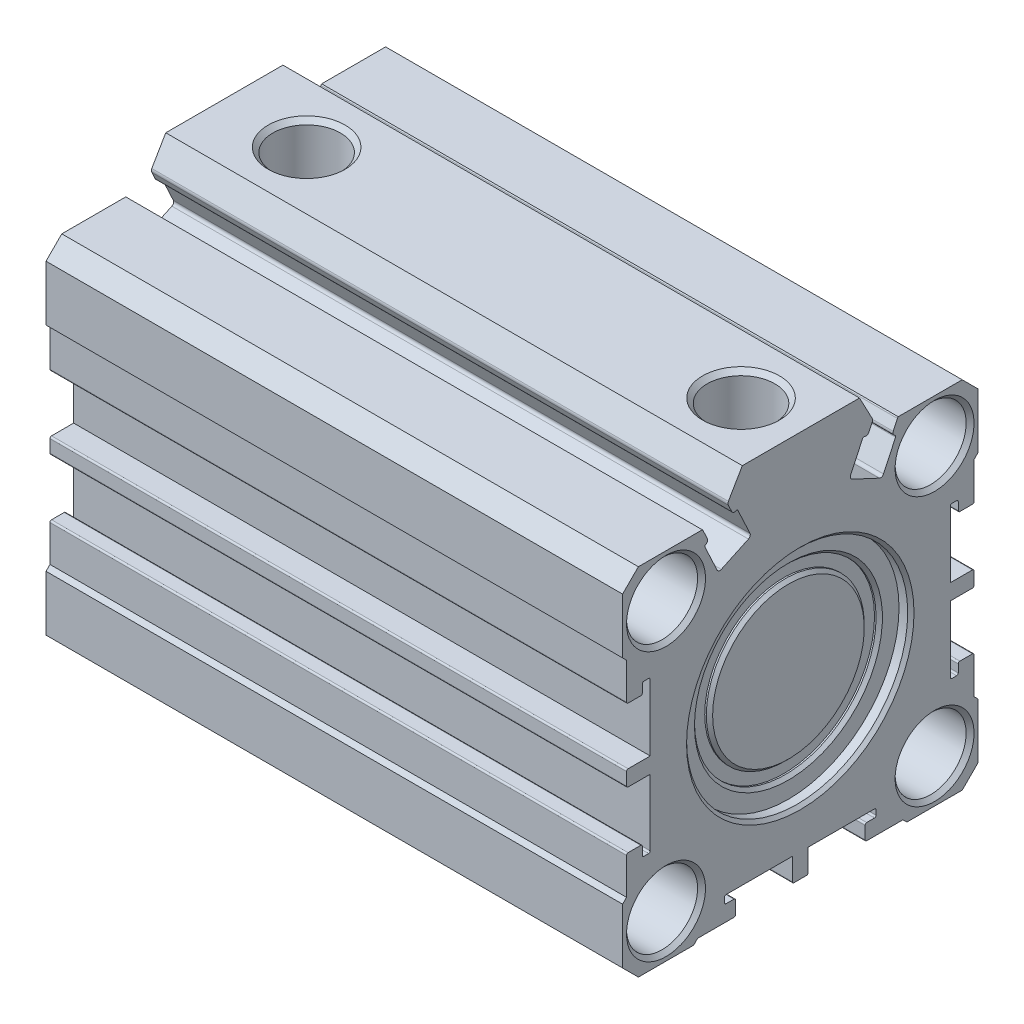
SolidWorks part; units mm, degrees
ref_plane "前视基准面" through (0, 0, 0) normal (0, 0, 1) x (1, 0, 0)
ref_plane "上视基准面" through (0, 0, 0) normal (0, 1, 0) x (1, 0, 0)
ref_plane "右视基准面" through (0, 0, 0) normal (1, 0, 0) x (0, 0, -1)
sketch "草图1" plane through (0, 0, 0) normal (1, 0, 0) x (0, 0, -1)
  line L0 (-22.5, -20.5) -> (-20.5, -22.5)
  line L1 (-20.5, -22.5) -> (-13.5, -22.5)
  line L2 (-13.5, -22.5) -> (-13, -22)
  line L3 (-13, -22) -> (-8.4, -22)
  line L4 (-8.2, -21.8) -> (-8.2, -20.2)
  line L5 (-8.4, -20) -> (-9.4, -20)
  line L6 (-9.6, -19.8) -> (-9.6, -19.2)
  line L7 (-9.4, -19) -> (-1, -19)
  line L8 (-1, -19) -> (-1, -21.8)
  line L9 (-0.8, -22) -> (0.8, -22)
  line L10 (1, -21.8) -> (1, -19)
  line L11 (1, -19) -> (9.4, -19)
  line L12 (9.6, -19.2) -> (9.6, -19.8)
  line L13 (9.4, -20) -> (8.4, -20)
  line L14 (8.2, -20.2) -> (8.2, -21.8)
  line L15 (8.4, -22) -> (13, -22)
  line L16 (13, -22) -> (13.5, -22.5)
  line L17 (13.5, -22.5) -> (20.5, -22.5)
  line L18 (20.5, -22.5) -> (22.5, -20.5)
  line L19 (22.5, -20.5) -> (22.5, -13.5)
  line L20 (22.5, -13.5) -> (22, -13)
  line L21 (22, -13) -> (22, -8.4)
  line L22 (21.8, -8.2) -> (20.2, -8.2)
  line L23 (20, -8.4) -> (20, -9.4)
  line L24 (19.8, -9.6) -> (19.2, -9.6)
  line L25 (19, -9.4) -> (19, -1)
  line L26 (19, -1) -> (21.8, -1)
  line L27 (22, -0.8) -> (22, 0.8)
  line L28 (21.8, 1) -> (19, 1)
  line L29 (19, 1) -> (19, 9.4)
  line L30 (19.2, 9.6) -> (19.8, 9.6)
  line L31 (20, 9.4) -> (20, 8.4)
  line L32 (20.2, 8.2) -> (21.8, 8.2)
  line L33 (22, 8.4) -> (22, 13)
  line L34 (22, 13) -> (22.5, 13.5)
  line L35 (22.5, 13.5) -> (22.5, 20.5)
  line L36 (22.5, 20.5) -> (20.5, 22.5)
  line L37 (20.5, 22.5) -> (12.3991, 22.5)
  line L38 (12.303, 22.3613) -> (11.7681, 21.2142)
  line L39 (12.0583, 20.4168) -> (10.5369, 17.1541)
  line L40 (10.0053, 16.9607) -> (6.5613, 18.5666)
  line L41 (6.3679, 19.0982) -> (7.8893, 22.3609)
  line L42 (8.6866, 22.6511) -> (9.1023, 23.5426)
  line L43 (9.0912, 23.9875) -> (7.499, 27)
  line L44 (7.499, 27) -> (-7.3373, 27)
  line L45 (-7.3373, 27) -> (-9.1053, 23.9744)
  line L46 (-9.1023, 23.5426) -> (-8.6866, 22.6511)
  line L47 (-7.8893, 22.3609) -> (-6.3679, 19.0982)
  line L48 (-6.5613, 18.5666) -> (-10.0053, 16.9607)
  line L49 (-10.5369, 17.1541) -> (-12.0583, 20.4168)
  line L50 (-11.7681, 21.2142) -> (-12.303, 22.3613)
  line L51 (-12.3991, 22.5) -> (-20.5, 22.5)
  line L52 (-20.5, 22.5) -> (-22.5, 20.5)
  line L53 (-22.5, 20.5) -> (-22.5, 13.5)
  line L54 (-22.5, 13.5) -> (-22, 13)
  line L55 (-22, 13) -> (-22, 8.4)
  line L56 (-21.8, 8.2) -> (-20.2, 8.2)
  line L57 (-20, 8.4) -> (-20, 9.4)
  line L58 (-19.8, 9.6) -> (-19.2, 9.6)
  line L59 (-19, 9.4) -> (-19, 1)
  line L60 (-19, 1) -> (-21.8, 1)
  line L61 (-22, 0.8) -> (-22, -0.8)
  line L62 (-21.8, -1) -> (-19, -1)
  line L63 (-19, -1) -> (-19, -9.4)
  line L64 (-19.2, -9.6) -> (-19.8, -9.6)
  line L65 (-20, -9.4) -> (-20, -8.4)
  line L66 (-20.2, -8.2) -> (-21.8, -8.2)
  line L67 (-22, -8.4) -> (-22, -13)
  line L68 (-22, -13) -> (-22.5, -13.5)
  line L69 (-22.5, -13.5) -> (-22.5, -20.5)
  arc A0 (-8.4, -22) -> (-8.2, -21.8) centre (-8.4, -21.8) ccw
  arc A1 (-8.2, -20.2) -> (-8.4, -20) centre (-8.4, -20.2) ccw
  arc A2 (-9.4, -20) -> (-9.6, -19.8) centre (-9.4, -19.8) cw
  arc A3 (-9.6, -19.2) -> (-9.4, -19) centre (-9.4, -19.2) cw
  arc A4 (-1, -21.8) -> (-0.8, -22) centre (-0.8, -21.8) ccw
  arc A5 (0.8, -22) -> (1, -21.8) centre (0.8, -21.8) ccw
  arc A6 (9.4, -19) -> (9.6, -19.2) centre (9.4, -19.2) cw
  arc A7 (9.6, -19.8) -> (9.4, -20) centre (9.4, -19.8) cw
  arc A8 (8.4, -20) -> (8.2, -20.2) centre (8.4, -20.2) ccw
  arc A9 (8.2, -21.8) -> (8.4, -22) centre (8.4, -21.8) ccw
  arc A10 (22, -8.4) -> (21.8, -8.2) centre (21.8, -8.4) ccw
  arc A11 (20.2, -8.2) -> (20, -8.4) centre (20.2, -8.4) ccw
  arc A12 (20, -9.4) -> (19.8, -9.6) centre (19.8, -9.4) cw
  arc A13 (19.2, -9.6) -> (19, -9.4) centre (19.2, -9.4) cw
  arc A14 (21.8, -1) -> (22, -0.8) centre (21.8, -0.8) ccw
  arc A15 (22, 0.8) -> (21.8, 1) centre (21.8, 0.8) ccw
  arc A16 (19, 9.4) -> (19.2, 9.6) centre (19.2, 9.4) cw
  arc A17 (19.8, 9.6) -> (20, 9.4) centre (19.8, 9.4) cw
  arc A18 (20, 8.4) -> (20.2, 8.2) centre (20.2, 8.4) ccw
  arc A19 (21.8, 8.2) -> (22, 8.4) centre (21.8, 8.4) ccw
  arc A20 (12.3991, 22.5) -> (12.303, 22.3613) centre (12.7561, 22.15) ccw
  arc A21 (11.7681, 21.2142) -> (11.9616, 20.6826) centre (12.1306, 21.0452) ccw
  arc A22 (11.9616, 20.6826) -> (12.0583, 20.4168) centre (11.877, 20.5014) cw
  arc A23 (10.5369, 17.1541) -> (10.0053, 16.9607) centre (10.1744, 17.3232) cw
  arc A24 (6.5613, 18.5666) -> (6.3679, 19.0982) centre (6.7304, 18.9291) cw
  arc A25 (7.8893, 22.3609) -> (8.1551, 22.4576) centre (8.0705, 22.2764) cw
  arc A26 (8.1551, 22.4576) -> (8.6866, 22.6511) centre (8.3241, 22.8201) ccw
  arc A27 (9.1023, 23.5426) -> (9.0912, 23.9875) centre (8.6492, 23.7539) ccw
  arc A28 (-9.1053, 23.9744) -> (-9.1023, 23.5426) centre (-8.6107, 23.7619) ccw
  arc A29 (-8.6866, 22.6511) -> (-8.1551, 22.4576) centre (-8.3241, 22.8201) ccw
  arc A30 (-8.1551, 22.4576) -> (-7.8893, 22.3609) centre (-8.0705, 22.2764) cw
  arc A31 (-6.3679, 19.0982) -> (-6.5613, 18.5666) centre (-6.7304, 18.9291) cw
  arc A32 (-10.0053, 16.9607) -> (-10.5369, 17.1541) centre (-10.1744, 17.3232) cw
  arc A33 (-12.0583, 20.4168) -> (-11.9616, 20.6826) centre (-11.877, 20.5014) cw
  arc A34 (-11.9616, 20.6826) -> (-11.7681, 21.2142) centre (-12.1306, 21.0452) ccw
  arc A35 (-12.303, 22.3613) -> (-12.3991, 22.5) centre (-12.7561, 22.15) ccw
  arc A36 (-22, 8.4) -> (-21.8, 8.2) centre (-21.8, 8.4) ccw
  arc A37 (-20.2, 8.2) -> (-20, 8.4) centre (-20.2, 8.4) ccw
  arc A38 (-20, 9.4) -> (-19.8, 9.6) centre (-19.8, 9.4) cw
  arc A39 (-19.2, 9.6) -> (-19, 9.4) centre (-19.2, 9.4) cw
  arc A40 (-21.8, 1) -> (-22, 0.8) centre (-21.8, 0.8) ccw
  arc A41 (-22, -0.8) -> (-21.8, -1) centre (-21.8, -0.8) ccw
  arc A42 (-19, -9.4) -> (-19.2, -9.6) centre (-19.2, -9.4) cw
  arc A43 (-19.8, -9.6) -> (-20, -9.4) centre (-19.8, -9.4) cw
  arc A44 (-20, -8.4) -> (-20.2, -8.2) centre (-20.2, -8.4) ccw
  arc A45 (-21.8, -8.2) -> (-22, -8.4) centre (-21.8, -8.4) ccw
extrude "凸台-拉伸1" add sketch "草图1" along normal blind 73
ref_plane "基准面1" through (0, 0, 17) normal (0, 0, 1) x (1, 0, 0)
sketch "草图2" plane through (0, 0, 17) normal (0, 0, 1) x (1, 0, 0)
  line L0 (0, -17) -> (0, -12)
  line L1 (0, -12) -> (0.5, -12.5)
  line L2 (0.5, -12.5) -> (7, -12.5)
  line L3 (7, -12.5) -> (7, -14)
  line L4 (7, -14) -> (7.5415, -14.5415)
  line L5 (7.5415, -14.5415) -> (36.5, -14.5415)
  line L6 (36.5, -14.5415) -> (36.5, -17)
  line L7 (36.5, -17) -> (0, -17)
  line L8 (36.5, -17) -> (0, -17) construction
revolve "切除-旋转1" cut sketch "草图2" angle 360 about L8 reverse direction yes
cosmetic thread "装饰螺纹线1" parameters "D1"=10, "D2"=6
cosmetic thread "装饰螺纹线2" parameters "D1"=10, "D2"=6
sketch "草图3" plane through (0, 0, 0) normal (1, 0, 0) x (0, 0, -1)
  line L0 (-17, -17) -> (17, -17)
  line L1 (-17, -17) -> (-17, 17)
pattern_linear "阵列(线性)1" count 2 spacing 34 along (0, 0, -1) count 2 spacing 34 along (0, 1, 0) of "切除-旋转1"
sketch "草图4" plane through (0, 0, 17) normal (0, 0, 1) x (1, 0, 0)
  line L0 (36.5, -17) -> (36.5, -14.5415)
  line L1 (36.5, -14.5415) -> (65.4585, -14.5415)
  line L2 (65.4585, -14.5415) -> (66, -14)
  line L3 (66, -14) -> (66, -12.5)
  line L4 (66, -12.5) -> (72.5, -12.5)
  line L5 (72.5, -12.5) -> (73, -12)
  line L6 (73, -12) -> (73, -17)
  line L7 (73, -17) -> (36.5, -17)
  line L8 (73, -17) -> (36.5, -17) construction
revolve "切除-旋转2" cut sketch "草图4" angle 360 about L8 reverse direction yes
ref_plane "基准面2" through (73, 0, 0) normal (1, 0, 0) x (0, 0, -1)
sketch "草图5" plane through (73, 0, 0) normal (1, 0, 0) x (0, 0, -1)
  line L0 (-17, -17) -> (17, -17)
  line L1 (-17, -17) -> (-17, 17)
pattern_linear "阵列(线性)2" count 2 spacing 34 along (0, 0, -1) count 2 spacing 34 along (0, 1, 0) of "切除-旋转2"
sketch "草图6" plane through (0, 0, 0) normal (0, 0, 1) x (1, 0, 0)
  line L0 (0, 0) -> (0, 8)
  line L1 (0, 8) -> (10.5, 8)
  line L2 (10.5, 8) -> (10.5, 16)
  line L3 (10.5, 16) -> (68.5, 16)
  line L4 (68.5, 16) -> (68.5, 0)
  line L5 (68.5, 0) -> (0, 0)
  line L6 (68.5, 0) -> (0, 0) construction
revolve "切除-旋转3" cut sketch "草图6" angle 360 about L6 reverse direction yes
sketch "草图7" plane through (0, 0, 0) normal (0, 0, 1) x (1, 0, 0)
  line L0 (0, 0) -> (0, 17.4)
  line L1 (0, 17.4) -> (0.4, 17)
  line L2 (0.4, 17) -> (3.1, 17)
  line L3 (3.1, 17) -> (3.1, 0)
  line L4 (3.1, 0) -> (0, 0)
  line L5 (3.1, 0) -> (0, 0) construction
revolve "切除-旋转4" cut sketch "草图7" angle 360 about L5 reverse direction yes
ref_plane "基准面3" through (1.6, 0, 0) normal (1, 0, 0) x (0, 0, -1)
hole_wizard "孔1" positions "草图9" profile "草图8" legacy
sketch "草图9" plane through (0, 27, 0) normal (0, 1, 0) x (1, 0, 0)
  point P0 (10.5, 0)
sketch "草图8" plane through (10.5, 27, 0) normal (1, 0, 0) x (0, 0, 1)
  line L0 (0, 0) -> (0, 8)
  line L1 (0, 8) -> (4.283, 8)
  line L2 (4.283, 8) -> (4.283, 0.581)
  line L3 (4.283, 0.581) -> (4.864, 0)
  line L4 (4.864, 0) -> (0, 0)
  line L5 (0, -6.4453) -> (0, 115.525) construction
  line L6 (-4.283, 0.581) -> (-4.864, 0) construction
  dimension "直径" = 8.566
  dimension "深度" = 8
  dimension "锥坑角度" = 90
  dimension "锥坑直径" = 9.728
cosmetic thread "装饰螺纹线3" parameters "D1"=8, "D2"=9.728
hole_wizard "孔2" positions "草图11" profile "草图10" legacy
sketch "草图11" plane through (0, 27, 0) normal (0, 1, 0) x (1, 0, 0)
  point P0 (65.5, 0)
sketch "草图10" plane through (65.5, 27, 0) normal (1, 0, 0) x (0, 0, 1)
  line L0 (0, 0) -> (0, 8)
  line L1 (0, 8) -> (4.283, 8)
  line L2 (4.283, 8) -> (4.283, 0.581)
  line L3 (4.283, 0.581) -> (4.864, 0)
  line L4 (4.864, 0) -> (0, 0)
  line L5 (0, -6.4453) -> (0, 115.525) construction
  line L6 (-4.283, 0.581) -> (-4.864, 0) construction
  dimension "直径" = 8.566
  dimension "深度" = 8
  dimension "锥坑角度" = 90
  dimension "锥坑直径" = 9.728
cosmetic thread "装饰螺纹线4" parameters "D1"=8, "D2"=9.728
sketch "草图12" plane through (0, 0, 0) normal (0, 0, 1) x (1, 0, 0)
  line L0 (0.6, 8) -> (3.1, 8)
  line L1 (3.1, 8) -> (3.1, 11.5)
  line L2 (3.1, 11.5) -> (1.1, 11.5)
  line L3 (0.6, 11) -> (0.6, 8)
  line L4 (3.1, 0) -> (0.6, 0) construction
  arc A0 (1.1, 11.5) -> (0.6, 11) centre (1.1, 11) ccw
revolve "旋转1" add sketch "草图12" angle 360 about L4 reverse direction yes
hole_wizard "孔3" positions "草图14" profile "草图13" legacy
sketch "草图14" plane through (73, 0, 0) normal (1, 0, 0) x (0, 0, -1)
  point P0 (0, 0)
sketch "草图13" plane through (73, 0, 0) normal (0, 1, 0) x (0, 0, -1)
  line L0 (0, 0) -> (0, 1.5)
  line L1 (0, 1.5) -> (14, 1.5)
  line L2 (14, 1.5) -> (14, 0.4)
  line L3 (14, 0.4) -> (14.4, 0)
  line L4 (14.4, 0) -> (0, 0)
  line L5 (0, -6.4453) -> (0, 115.525) construction
  line L6 (-14, 0.4) -> (-14.4, 0) construction
  dimension "直径" = 28
  dimension "深度" = 1.5
  dimension "锥坑角度" = 90
  dimension "锥坑直径" = 28.8
ref_plane "基准面4" through (73, 0, 0) normal (1, 0, 0) x (0, 0, -1)
ref_plane "基准面5" through (0, 19, 0) normal (0, 1, 0) x (1, 0, 0)
sketch "草图15" plane through (0, 0, 0) normal (0, 0, 1) x (1, 0, 0)
  line L0 (70.9, 11.5) -> (70.9, 10)
  line L1 (70.9, 10) -> (71.1, 10)
  line L2 (71.1, 10) -> (71.5, 9.6)
  line L3 (71.5, 9.6) -> (71.5, 11.9)
  line L4 (71.5, 11.9) -> (71.1, 11.5)
  line L5 (71.1, 11.5) -> (70.9, 11.5)
  line L6 (50, 0) -> (-50, 0) construction
revolve "切除-旋转5" cut sketch "草图15" angle 360 about L6 reverse direction yes
ref_plane "基准面6" through (1, 0, 0) normal (1, 0, 0) x (0, 0, -1)
ref_plane "基准面7" through (72, 0, 0) normal (1, 0, 0) x (0, 0, -1)
ref_plane "IP_SWITCH1 XY" through (1, 0, 0) normal (-1, 0, 0) x (0, 0, 1)
ref_plane "IP_SWITCH1 XZ" through (0, 17.7636, 0) normal (0, 1, 0) x (1, 0, 0)
ref_plane "IP_SWITCH1 YZ" through (0, 0, -8.2833) normal (0, 0, -1) x (-1, 0, 0)
ref_axis "IP_SWITCH1 X" through (1, 17.7636, 80.9) along (0, 0, -1)
ref_axis "IP_SWITCH1 Y" through (1, 50, -8.2833) along (0, -1, 0)
ref_axis "IP_SWITCH1 Z" through (-80.9, 17.7636, -8.2833) along (1, 0, 0)
sketch3d "IP_SWITCH1"
  point P0 (1, 17.7636, -8.2833)
ref_plane "IP_SWITCH2 XY" through (72, 0, 0) normal (1, 0, 0) x (0, 0, -1)
ref_plane "IP_SWITCH2 XZ" through (0, 17.7636, 0) normal (0, -1, 0) x (-1, 0, 0)
ref_plane "IP_SWITCH2 YZ" through (0, 0, 8.2833) normal (0, 0, -1) x (-1, 0, 0)
ref_axis "IP_SWITCH2 X" through (72, 17.7636, 80.9) along (0, 0, -1)
ref_axis "IP_SWITCH2 Y" through (72, -50, 8.2833) along (0, 1, 0)
ref_axis "IP_SWITCH2 Z" through (80.9, 17.7636, 8.2833) along (-1, 0, 0)
sketch3d "IP_SWITCH2"
  point P0 (72, 17.7636, 8.2833)
ref_plane "IP_SWITCH3 XY" through (1, 0, 0) normal (-1, 0, 0) x (0, 0, 1)
ref_plane "IP_SWITCH3 XZ" through (0, 1, 0) normal (0, 1, 0) x (1, 0, 0)
ref_plane "IP_SWITCH3 YZ" through (0, 0, -19) normal (0, 0, -1) x (-1, 0, 0)
ref_axis "IP_SWITCH3 X" through (1, 1, 80.9) along (0, 0, -1)
ref_axis "IP_SWITCH3 Y" through (1, 50, -19) along (0, -1, 0)
ref_axis "IP_SWITCH3 Z" through (-80.9, 1, -19) along (1, 0, 0)
sketch3d "IP_SWITCH3"
  point P0 (1, 1, -19)
ref_plane "IP_SWITCH4 XY" through (72, 0, 0) normal (1, 0, 0) x (0, 0, -1)
ref_plane "IP_SWITCH4 XZ" through (0, -1, 0) normal (0, -1, 0) x (-1, 0, 0)
ref_plane "IP_SWITCH4 YZ" through (0, 0, 19) normal (0, 0, -1) x (-1, 0, 0)
ref_axis "IP_SWITCH4 X" through (72, -1, 80.9) along (0, 0, -1)
ref_axis "IP_SWITCH4 Y" through (72, -50, 19) along (0, 1, 0)
ref_axis "IP_SWITCH4 Z" through (80.9, -1, 19) along (-1, 0, 0)
sketch3d "IP_SWITCH4"
  point P0 (72, -1, 19)
ref_plane "for_dummy XY" through (0, 0, 0) normal (-1, 0, 0) x (0, 0, 1)
ref_plane "for_dummy XZ" through (0, 0, 0) normal (0, 1, 0) x (1, 0, 0)
ref_plane "for_dummy YZ" through (0, 0, 0) normal (0, 0, -1) x (-1, 0, 0)
ref_axis "for_dummy X" through (0, 0, 80.9) along (0, 0, -1)
ref_axis "for_dummy Y" through (0, 50, 0) along (0, -1, 0)
ref_axis "for_dummy Z" through (-80.9, 0, 0) along (1, 0, 0)
sketch3d "for_dummy"
  point P0 (0, 0, 0)
ref_plane "for_mouanting XY" through (73, 0, 0) normal (1, 0, 0) x (0, 0, -1)
ref_plane "for_mouanting XZ" through (0, 0, 0) normal (0, -1, 0) x (-1, 0, 0)
ref_plane "for_mouanting YZ" through (0, 0, 0) normal (0, 0, -1) x (-1, 0, 0)
ref_axis "for_mouanting X" through (73, 0, 80.9) along (0, 0, -1)
ref_axis "for_mouanting Y" through (73, -50, 0) along (0, 1, 0)
ref_axis "for_mouanting Z" through (80.9, 0, 0) along (-1, 0, 0)
sketch3d "for_mouanting"
  point P0 (73, 0, 0)
ref_plane "for_s XY" through (0, 19, 0) normal (0, 1, 0) x (1, 0, 0)
ref_plane "for_s XZ" through (0, 0, 0) normal (0, 0, 1) x (1, 0, 0)
ref_plane "for_s YZ" through (10.5, 0, 0) normal (1, 0, 0) x (0, 0, -1)
ref_axis "for_s X" through (-80.9, 19, 0) along (1, 0, 0)
ref_axis "for_s Y" through (10.5, 19, 50) along (0, 0, -1)
ref_axis "for_s Z" through (10.5, 50, 0) along (0, -1, 0)
sketch3d "for_s"
  point P0 (10.5, 19, 0)
ref_plane "for_s_2 XY" through (0, 19, 0) normal (0, 1, 0) x (1, 0, 0)
ref_plane "for_s_2 XZ" through (0, 0, 0) normal (0, 0, 1) x (1, 0, 0)
ref_plane "for_s_2 YZ" through (65.5, 0, 0) normal (1, 0, 0) x (0, 0, -1)
ref_axis "for_s_2 X" through (-80.9, 19, 0) along (1, 0, 0)
ref_axis "for_s_2 Y" through (65.5, 19, 50) along (0, 0, -1)
ref_axis "for_s_2 Z" through (65.5, 50, 0) along (0, -1, 0)
sketch3d "for_s_2"
  point P0 (65.5, 19, 0)
